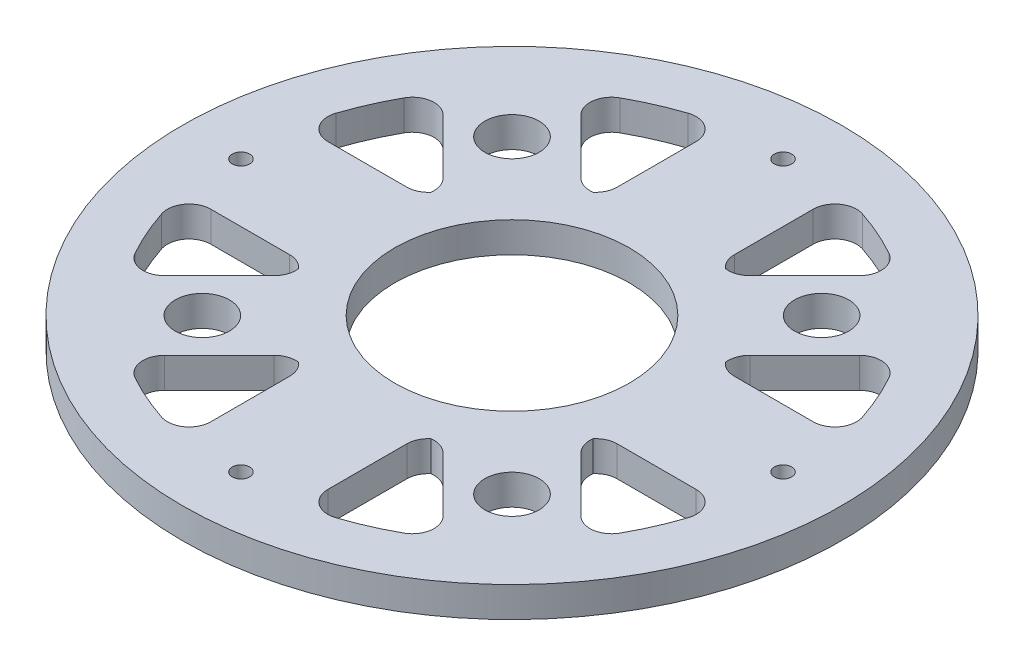
SolidWorks part; units mm, degrees
material "Custom Plastic"
ref_plane "Front Plane" through (0, 0, 0) normal (0, 0, 1) x (1, 0, 0)
ref_plane "Top Plane" through (0, 0, 0) normal (0, 1, 0) x (1, 0, 0)
ref_plane "Right Plane" through (0, 0, 0) normal (1, 0, 0) x (0, 0, -1)
sketch "Sketch1" plane through (0, 0, 0) normal (0, 1, 0) x (1, 0, 0)
  circle A0 centre (0, 0) radius 76
  circle A1 centre (0, 0) radius 27.051
  circle A2 centre (0, 0) radius 62.5 construction
  circle A3 centre (0, 62.5) radius 2
  circle A4 centre (62.5, 0) radius 2
  circle A5 centre (0, -62.5) radius 2
  circle A6 centre (-62.5, 0) radius 2
  dimension "D1" = 152
  dimension "D2" = 54.102
  dimension "D3" = 125
  dimension "D4" = 4
extrude "Boss-Extrude1" add sketch "Sketch1" along normal blind 7
sketch "Sketch3" plane through (0, 0, 0) normal (0, -1, 0) x (1, 0, 0)
  circle A0 centre (0, 0) radius 27.051
sketch "Sketch4" plane through (0, 7, 0) normal (0, 1, 0) x (1, 0, 0)
  line L0 (134.0846, 0) -> (0, 0) construction
  line L1 (0, 0) -> (0, 97.8812) construction
  line L2 (13.5, 62.5) -> (13.5, 34.504)
  line L3 (34.504, 13.5) -> (62.5, 13.5)
  line L4 (-34.504, 13.5) -> (-62.5, 13.5)
  line L5 (-13.5, 62.5) -> (-13.5, 34.504)
  line L6 (34.504, -13.5) -> (62.5, -13.5)
  line L7 (13.5, -62.5) -> (13.5, -34.504)
  line L8 (-13.5, -62.5) -> (-13.5, -34.504)
  line L9 (-34.504, -13.5) -> (-62.5, -13.5)
  line L10 (26.199, 26.199) -> (45.2134, 45.2134)
  line L11 (0, 0) -> (72.917, 72.917) construction
  line L12 (36.5531, 52.463) -> (17.0072, 32.9171)
  line L13 (52.463, 36.5531) -> (32.9171, 17.0072)
  line L14 (36.5531, -52.463) -> (17.0072, -32.9171)
  line L15 (52.463, -36.5531) -> (32.9171, -17.0072)
  line L16 (-52.463, -36.5531) -> (-32.9171, -17.0072)
  line L17 (-36.5531, -52.463) -> (-17.0072, -32.9171)
  line L18 (-52.463, 36.5531) -> (-32.9171, 17.0072)
  line L19 (-36.5531, 52.463) -> (-17.0072, 32.9171)
  arc A0 (13.5, 62.5) -> (62.5, 13.5) centre (0, 0) cw
  circle A1 centre (35.7062, 35.7062) radius 6.25
  circle A2 centre (35.7062, 35.7062) radius 11.25
  circle A5 centre (35.7062, -35.7062) radius 6.25
  arc A7 (-13.5, 62.5) -> (-62.5, 13.5) centre (0, 0) ccw
  arc A8 (13.5, -62.5) -> (62.5, -13.5) centre (0, 0) ccw
  arc A10 (-13.5, -62.5) -> (-62.5, -13.5) centre (0, 0) cw
  circle A11 centre (0, 0) radius 37.051
  circle A12 centre (0, 0) radius 27.051 construction
  circle A13 centre (35.7062, -35.7062) radius 11.25
  circle A14 centre (-35.7062, -35.7062) radius 6.25
  circle A15 centre (-35.7062, -35.7062) radius 11.25
  circle A16 centre (-35.7062, 35.7062) radius 6.25
  circle A17 centre (-35.7062, 35.7062) radius 11.25
  dimension "D1" = 10
  dimension "D4" = 63.9414
  dimension "D6" = 12.5
  dimension "D7" = 5
  dimension "D2" = 27
  dimension "D3" = 27
  dimension "D5" = 45
extrude "Cut-Extrude1" cut sketch "Sketch4" against normal blind 10 contours A11 L7 A8 L14 | A11 L15 A8 L6 | A11 L17 A10 L8 | A11 L9 A10 L16 | A11 L18 A7 L4 | A11 L5 A7 L19 | A11 L12 A0 L2 | A11 L3 A0 L13 | A1 | A5 | A14 | A16 region at (21.5497, 7, -49.012) region at (-21.5497, 7, -49.012) region at (49.012, 7, -21.5497) region at (-49.012, 7, -21.5497) region at (-49.012, 7, 21.5497) region at (49.012, 7, 21.5497) region at (-21.5497, 7, 49.012) region at (21.5497, 7, 49.012)
fillet "Fillet1" radius 5 32 edges at (34.504, 3.5, 13.5) (62.5, 3.5, 13.5) (52.463, 3.5, 36.5531) (32.9171, 3.5, 17.0072) (32.9171, 3.5, -17.0072) (34.504, 3.5, -13.5) (62.5, 3.5, -13.5) (52.463, 3.5, -36.5531) (36.5531, 3.5, -52.463) (13.5, 3.5, -62.5) (13.5, 3.5, -34.504) (17.0072, 3.5, -32.9171) (-17.0072, 3.5, -32.9171) (-36.5531, 3.5, -52.463) (-13.5, 3.5, -34.504) (-13.5, 3.5, -62.5) (-32.9171, 3.5, -17.0072) (-52.463, 3.5, -36.5531) (-62.5, 3.5, -13.5) (-34.504, 3.5, -13.5) (-32.9171, 3.5, 17.0072) (-34.504, 3.5, 13.5) (-62.5, 3.5, 13.5) (-52.463, 3.5, 36.5531) (-36.5531, 3.5, 52.463) (-13.5, 3.5, 62.5) (-13.5, 3.5, 34.504) (-17.0072, 3.5, 32.9171) (17.0072, 3.5, 32.9171) (13.5, 3.5, 34.504) (13.5, 3.5, 62.5) (36.5531, 3.5, 52.463)
